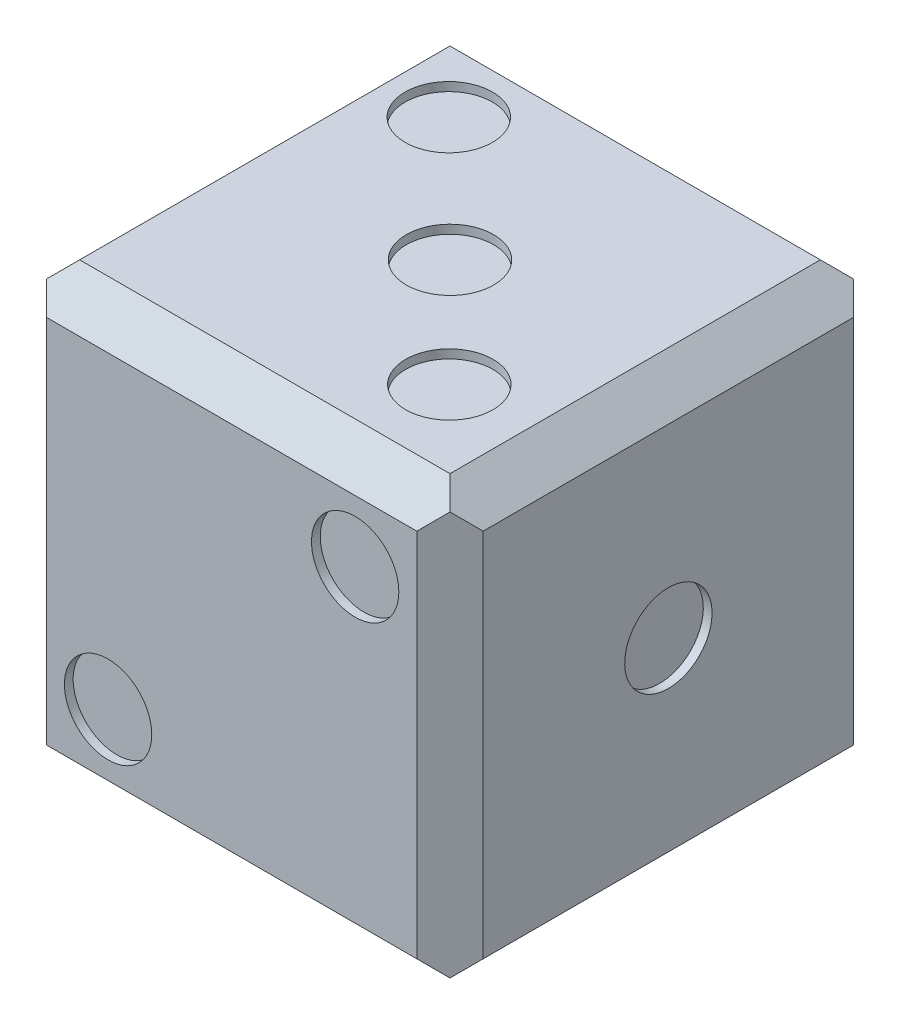
SolidWorks part; units mm, degrees
ref_plane "Front Plane" through (0, 0, 0) normal (0, 0, 1) x (1, 0, 0)
ref_plane "Top Plane" through (0, 0, 0) normal (0, 1, 0) x (1, 0, 0)
ref_plane "Right Plane" through (0, 0, 0) normal (1, 0, 0) x (0, 0, -1)
sketch "Sketch1" plane through (0, 0, 0) normal (0, 0, 1) x (1, 0, 0)
  line L1 (0, 0) -> (127, 0)
  line L2 (0, 0) -> (0, 127)
  line L3 (0, 127) -> (127, 127)
  line L4 (127, 0) -> (127, 127)
  dimension "D1" = 127
extrude "Cube" add sketch "Sketch1" along normal blind 127
sketch "Sketch3" plane through (0, 0, 0) normal (0, 1, 0) x (1, 0, 0)
extrude "Boss-Extrude2" add sketch "Sketch1<2>" along normal blind 127
sketch "Sketch1<2>" plane through (0, 0, 0) normal (0, 0, 1) x (1, 0, 0) same geometry as "Sketch1"
sketch "Sketch4" plane through (0, 0, 0) normal (0, 0, -1) x (-1, 0, 0)
  line L0 (0, 0) -> (-127, 127) construction
  line L1 (-95.25, 63.5) -> (-31.75, 63.5) construction
  line L2 (-63.5, 80.5433) -> (-63.5, 46.4567) construction
  circle A0 centre (-31.75, 63.5) radius 12.7
  circle A1 centre (-31.75, 31.75) radius 12.7
  circle A2 centre (-31.75, 63.5) radius 12.7
  circle A3 centre (-31.75, 95.25) radius 12.7
  circle A4 centre (-95.25, 31.75) radius 12.7
  circle A5 centre (-95.25, 63.5) radius 12.7
  circle A6 centre (-95.25, 95.25) radius 12.7
  point P7 (-63.5, 63.5)
  point P21 (0, 0)
  point P22 (0, 0)
  point P23 (-63.5, 64.7038)
  dimension "D2" = 25.4
  dimension "D5" = 31.75
  dimension "D1" = 63.5
  dimension "D6" = 44.9013
  dimension "D7" = 44.9013
  dimension "D3" = 2
  dimension "D4" = 2
sketch "Sketch5" plane through (0, 0, 127) normal (0, 0, 1) x (1, 0, 0)
sketch "Sketch7" plane through (0, 0, 0) normal (0, 0, -1) x (-1, 0, 0)
extrude "6-dot cut" cut sketch "Sketch4" against normal blind 2.54 contours A3 | A0 | A1 | A4 | A5 | A6
sketch "Sketch9" plane through (0, 0, 0) normal (-1, 0, 0) x (0, 0, 1)
  line L0 (31.75, 63.5) -> (95.25, 63.5) construction
  line L1 (0, 0) -> (127, 127) construction
  line L2 (95.25, 63.5) -> (95.25, 101.6) construction
  line L3 (63.5, 85.838) -> (63.5, 45.1601) construction
  circle A0 centre (95.25, 101.6) radius 12.7
  circle A1 centre (95.25, 38.1) radius 12.7
  circle A2 centre (31.75, 38.1) radius 12.7
  circle A3 centre (31.75, 101.6) radius 12.7
  point P0 (63.5, 63.5)
  dimension "D3" = 25.4
  dimension "D5" = 25.4
  dimension "D1" = 63.5
  dimension "D2" = 38.1
  dimension "D6" = 63.5
  dimension "D4" = 2
extrude "4-dot cut" cut sketch "Sketch9" against normal blind 2.54 contours A3 | A2 | A1 | A0
sketch "Sketch10" plane through (0, 127, 0) normal (0, 1, 0) x (1, 0, 0)
  line L0 (0, 0) -> (127, -127) construction
  circle A0 centre (63.5, -63.5) radius 12.7
  circle A1 centre (27.4038, -27.755) radius 12.7
  circle A2 centre (94.7988, -94.9889) radius 12.7
  point P2 (63.5, -63.5)
  point P9 (30.934, -31.2508)
  point P12 (94.7988, -94.9889)
  dimension "D1" = 25.4
  dimension "D3" = 44.3978
  dimension "D4" = 39.004
  dimension "D2" = 50.8
  dimension "D5" = 134.2002
extrude "3-dot cut" cut sketch "Sketch10" against normal blind 2.54 contours A1 | A0 | A2
sketch "Sketch11" plane through (0, 0, 0) normal (0, -1, 0) x (1, 0, 0)
  line L0 (0, 0) -> (127, 127) construction
  line L1 (0, 127) -> (127, 0) construction
  circle A0 centre (63.5, 63.5) radius 12.7
  circle A1 centre (27.579, 27.579) radius 12.7
  circle A2 centre (99.421, 99.421) radius 12.7
  circle A3 centre (27.579, 99.421) radius 12.7
  circle A4 centre (99.421, 27.579) radius 12.7
  point P16 (22.1907, 104.9994)
  point P19 (96.4461, 30.2371)
  dimension "D1" = 25.4
  dimension "D2" = 50.8
  dimension "D3" = 50.8
  dimension "D4" = 50.8
  dimension "D5" = 50.8
extrude "5-dot cut" cut sketch "Sketch11" against normal blind 2.54 contours A3 | A2 | A0 | A4 | A1
sketch "Sketch12" plane through (127, 0, 0) normal (1, 0, 0) x (0, 0, -1)
  line L0 (0, 0) -> (-127, 127) construction
  circle A0 centre (-63.5, 63.5) radius 12.7
  dimension "D1" = 25.4
extrude "1-dot cut" cut sketch "Sketch12" against normal blind 2.54 contours A0
sketch "Sketch13" plane through (0, 0, 127) normal (0, 0, 1) x (1, 0, 0)
  line L0 (0, 0) -> (127, 127) construction
  circle A1 centre (27.579, 27.579) radius 12.7
  circle A2 centre (99.421, 99.421) radius 12.7
  point P4 (63.5, 63.5)
  point P10 (28.6532, 28.4631)
  point P11 (102.4017, 102.085)
  dimension "D1" = 50.8
  dimension "D2" = 25.4
  dimension "D3" = 50.8
extrude "2-dot cut" cut sketch "Sketch13" against normal blind 2.54 contours A1 | A2
sketch "Sketch16" plane through (0, 0, 0) normal (-1, 0, 0) x (0, 0, 1)
  line L0 (0, 127) -> (9.652, 127)
  line L1 (127, 127) -> (0, 127) construction
  line L2 (9.652, 127) -> (0, 117.348)
  line L3 (0, 127) -> (0, 0) construction
  line L4 (0, 117.348) -> (0, 127)
  line L5 (0, 63.5) -> (127, 63.5) construction
  line L6 (127, 127) -> (127, 0) construction
  line L7 (63.5, 127) -> (63.5, 0) construction
  line L8 (127, 0) -> (0, 0) construction
  line L9 (117.348, 127) -> (127, 117.348)
  line L10 (127, 127) -> (117.348, 127)
  line L11 (127, 117.348) -> (127, 127)
  line L13 (127, 0) -> (117.348, 0)
  line L14 (127, 9.652) -> (127, 0)
  line L15 (117.348, 0) -> (127, 9.652)
  line L16 (9.652, 0) -> (0, 9.652)
  line L17 (0, 0) -> (9.652, 0)
  line L18 (0, 9.652) -> (0, 0)
  dimension "D1" = 9.652
extrude "Cut-Extrude7" cut sketch "Sketch16" against normal up to next
sketch "Sketch17" plane through (0, 0, 127) normal (0, 0, 1) x (1, 0, 0)
  line L0 (9.652, 127) -> (0, 127)
  line L1 (127, 127) -> (0, 127) construction
  line L2 (9.652, 127) -> (0, 117.348)
  line L3 (127, 117.348) -> (0, 117.348) construction
  line L4 (0, -69.85) -> (0, 69.85) construction
  line L5 (0, 127) -> (0, 117.348) construction
  line L6 (63.5, 127) -> (63.5, 0) construction
  line L7 (127, 0) -> (0, 0) construction
  line L8 (127, 63.5) -> (0, 63.5) construction
  line L9 (127, 9.652) -> (127, 117.348) construction
  line L10 (0, 117.348) -> (0, 9.652) construction
  line L12 (0, 127) -> (0, 117.348)
  line L13 (117.348, 127) -> (127, 117.348)
  line L14 (117.348, 127) -> (127, 127)
  line L15 (127, 127) -> (127, 117.348)
  line L16 (117.348, 0) -> (127, 0)
  line L17 (127, 0) -> (127, 9.652)
  line L18 (117.348, 0) -> (127, 9.652)
  line L19 (9.652, 0) -> (0, 0)
  line L20 (9.652, 0) -> (0, 9.652)
  line L21 (0, 0) -> (0, 9.652)
extrude "Cut-Extrude8" cut sketch "Sketch17" against normal up to next
sketch "Sketch18" plane through (0, 127, 0) normal (0, 1, 0) x (1, 0, 0)
  line L0 (0, 0) -> (9.652, 0)
  line L1 (-69.85, 0) -> (69.85, 0) construction
  line L2 (9.652, 0) -> (0, -9.652)
  line L3 (0, -69.85) -> (0, 69.85) construction
  line L4 (0, -9.652) -> (0, 0)
  line L5 (117.348, -9.652) -> (9.652, -9.652) construction
  line L6 (63.5, -9.652) -> (63.5, -117.348) construction
  line L7 (117.348, -117.348) -> (9.652, -117.348) construction
  line L8 (9.652, -9.652) -> (9.652, -117.348) construction
  line L9 (9.652, -63.5) -> (117.348, -63.5) construction
  line L10 (117.348, -9.652) -> (117.348, -117.348) construction
  line L11 (117.348, 0) -> (127, -9.652)
  line L12 (127, 0) -> (117.348, 0)
  line L13 (127, -9.652) -> (127, 0)
  line L14 (127, -127) -> (117.348, -127)
  line L15 (127, -117.348) -> (127, -127)
  line L16 (117.348, -127) -> (127, -117.348)
  line L17 (9.652, -127) -> (0, -117.348)
  line L18 (0, -127) -> (9.652, -127)
  line L19 (0, -117.348) -> (0, -127)
  dimension "D1" = 9.652
extrude "Cut-Extrude9" cut sketch "Sketch18" against normal up to next
